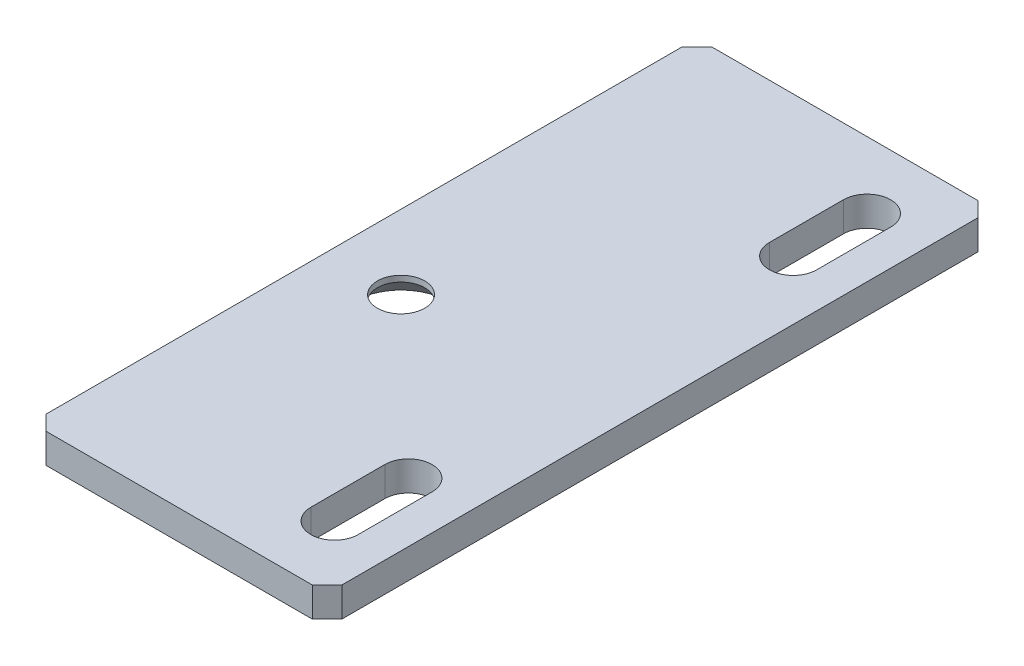
SolidWorks part; units mm, degrees
material "6061 Alloy"
ref_plane "Front Plane" through (0, 0, 0) normal (0, 0, 1) x (1, 0, 0)
ref_plane "Top Plane" through (0, 0, 0) normal (0, 1, 0) x (1, 0, 0)
ref_plane "Right Plane" through (0, 0, 0) normal (1, 0, 0) x (0, 0, -1)
sketch "Sketch1" plane through (0, 0, 0) normal (0, 1, 0) x (1, 0, 0)
  line L5 (10, -22.5) -> (-10, -22.5)
  line L6 (10, -22.5) -> (10, 22.5)
  line L7 (10, 22.5) -> (-10, 22.5)
  line L8 (-10, -22.5) -> (-10, 22.5)
  line L9 (10, -22.5) -> (-10, 22.5) construction
  line L10 (10, 22.5) -> (-10, -22.5) construction
  point P0 (0, 0)
  dimension "D3" = 20
  dimension "D4" = 45
extrude "Base" add sketch "Sketch1" along normal blind 2
sketch "Sketch6" plane through (0, 2, 0) normal (0, 1, 0) x (1, 0, 0)
  line L0 (6, 18) -> (6, 13) construction
  line L1 (7.6, 18) -> (7.6, 13)
  line L2 (4.4, 18) -> (4.4, 13)
  line L3 (6, -13) -> (6, -18) construction
  line L4 (7.6, -13) -> (7.6, -18)
  line L5 (4.4, -13) -> (4.4, -18)
  line L6 (0, 0) -> (-4.8321, 0) construction
  line L7 (10, -22.5) -> (10, 22.5) construction
  line L8 (10, 22.5) -> (-10, 22.5) construction
  arc A0 (7.6, 18) -> (4.4, 18) centre (6, 18) ccw
  arc A1 (4.4, 13) -> (7.6, 13) centre (6, 13) ccw
  arc A2 (7.6, -13) -> (4.4, -13) centre (6, -13) ccw
  arc A3 (4.4, -18) -> (7.6, -18) centre (6, -18) ccw
  point P3 (6, 15.5)
  point P8 (6, -15.5)
  dimension "D1" = 3.2
  dimension "D2" = 5
  dimension "D3" = 31
  dimension "D4" = 4
  dimension "D5" = 4.5
extrude "ScrewSlots" cut sketch "Sketch6" against normal through all
hole_wizard "PulleyHole" positions "Sketch4" profile "Sketch5" countersink size "M3" standard "ANSI Metric" end condition through all
sketch "Sketch4" plane through (0, 0, 0) normal (0, -1, 0) x (-1, 0, 0)
  line L2 (-10, -22.5) -> (-10, 22.5) construction
  line L4 (-10, 22.5) -> (10, 22.5) construction
  point P0 (5, -2.5)
  dimension "D1" = 25
  dimension "D2" = 15
sketch "Sketch5" plane through (-5, 0, 2.5) normal (1, 0, 0) x (0, 0, -1)
  line L0 (0, 0) -> (0, 2)
  line L1 (0, 2) -> (1.6, 2)
  line L2 (1.6, 2) -> (1.6, 1.6)
  line L3 (1.6, 1.6) -> (3.2, 0)
  line L5 (3.2, 0) -> (0, 0)
  line L6 (-1.6, 1.6) -> (-3.2, 0) construction
  line L11 (0, -6.35) -> (0, 107.95) construction
  dimension "Thru Hole Dia." = 3.2
  dimension "Thru Hole Depth" = 2
  dimension "Near C'Sink Dia." = 6.4
  dimension "Near C'Sink Angle" = 90
chamfer "Chamfer1" distance 1 angle 45 4 edges at (-10, 1, -22.5) (10, 1, -22.5) (10, 1, 22.5) (-10, 1, 22.5)
